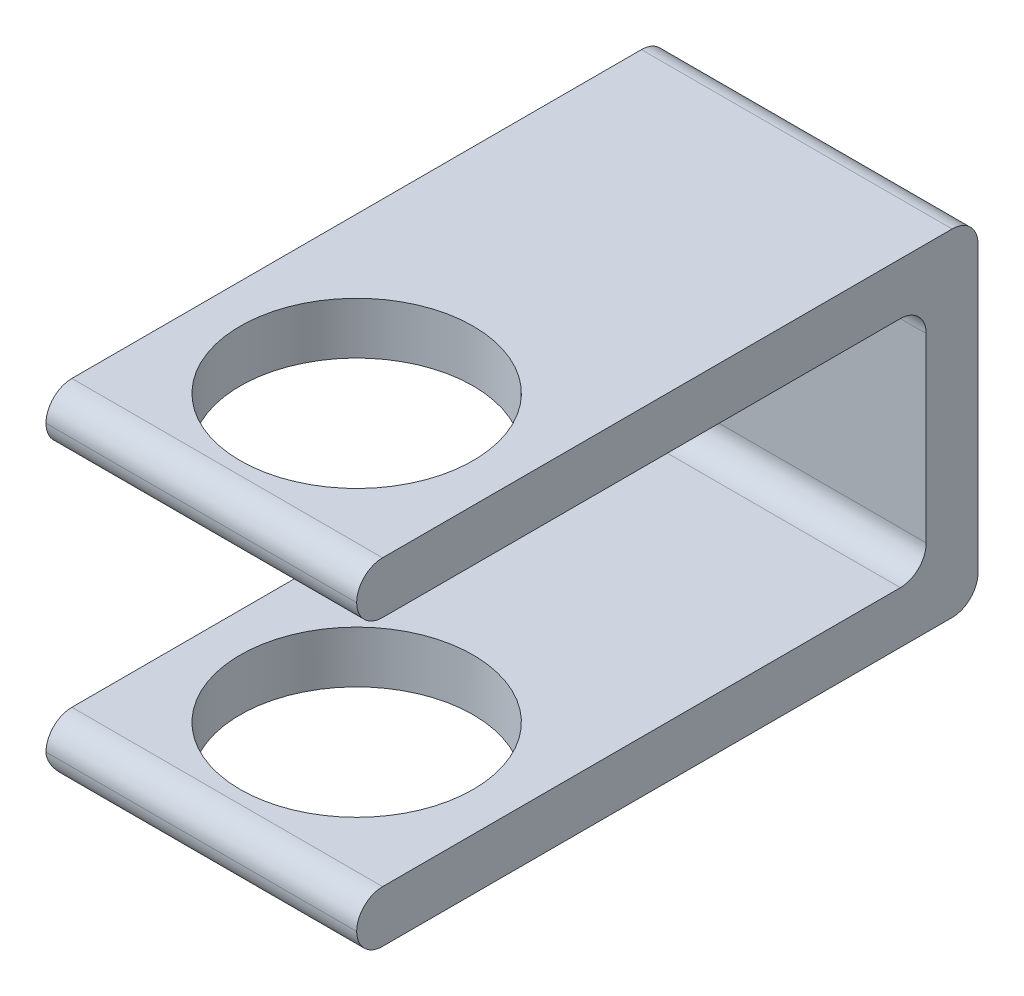
SolidWorks part; units mm, degrees
ref_plane "Front Plane" through (0, 0, 0) normal (0, 0, 1) x (1, 0, 0)
ref_plane "Top Plane" through (0, 0, 0) normal (0, 1, 0) x (1, 0, 0)
ref_plane "Right Plane" through (0, 0, 0) normal (1, 0, 0) x (0, 0, -1)
sketch "Sketch1" plane through (0, 0, 0) normal (0, 1, 0) x (1, 0, 0)
  line L1 (-19.05, -38.1) -> (19.05, -38.1)
  line L2 (-19.05, -38.1) -> (-19.05, 38.1)
  line L3 (-19.05, 38.1) -> (19.05, 38.1)
  line L4 (19.05, -38.1) -> (19.05, 38.1)
  line L5 (-19.05, -38.1) -> (19.05, 38.1) construction
  line L6 (-19.05, 38.1) -> (19.05, -38.1) construction
  point P0 (0, 0)
  dimension "D1" = 38.1
  dimension "D2" = 76.2
extrude "Boss-Extrude1" add sketch "Sketch1" along normal blind 41.275
sketch "Sketch2" plane through (0, 0, 38.1) normal (0, 0, 1) x (1, 0, 0)
  line L0 (-19.05, 41.275) -> (-19.05, 0) construction
  line L1 (-19.05, 34.925) -> (19.05, 34.925)
  line L2 (-19.05, 34.925) -> (-19.05, 6.35)
  line L3 (-19.05, 6.35) -> (19.05, 6.35)
  line L4 (19.05, 34.925) -> (19.05, 6.35)
  line L5 (19.05, 41.275) -> (19.05, 0) construction
  line L6 (-19.05, 41.275) -> (19.05, 41.275) construction
  line L7 (-19.05, 0) -> (19.05, 0) construction
  dimension "D1" = 6.35
  dimension "D2" = 6.35
extrude "Cut-Extrude1" cut sketch "Sketch2" against normal offset from surface (69.85 mm away) 6.35 up to face at (0, 20.6375, -38.1)
sketch "Sketch3" plane through (0, 41.275, 0) normal (0, 1, 0) x (1, 0, 0)
  line L1 (19.05, 38.1) -> (-19.05, 38.1) construction
  line L3 (3.6662, -12.7) -> (-3.6662, -12.7)
  line L4 (-3.6662, -12.7) -> (-7.3323, -19.05)
  line L5 (-7.3323, -19.05) -> (-3.6662, -25.4)
  line L6 (-3.6662, -25.4) -> (3.6662, -25.4)
  line L7 (3.6662, -25.4) -> (7.3323, -19.05)
  line L8 (7.3323, -19.05) -> (3.6662, -12.7)
  circle A0 centre (0, -19.05) radius 50.8
  circle A1 centre (0, -19.05) radius 6.35 construction
  circle A2 centre (0, -19.05) radius 14.2875
  dimension "D1" = 101.6
  dimension "D2" = 6.35
  dimension "D3" = 12.7
  dimension "D4" = 28.575
extrude "Cut-Extrude2" cut sketch "Sketch3" against normal through all contours L7 L8 L3 L4 L5 L6 | A2 L8 L7 L6 L5 L4 L3 region at (0, 41.275, 19.05) region at (-13.8834, 41.275, 19.05)
fillet "Fillet1" radius 3.175 9 edges at (0, 41.275, 38.1) (0, 0, -38.1) (0, 0, 38.1) (0, 6.35, 38.1) (0, 6.35, -31.75) (0, 34.925, -31.75) (0, 34.925, 38.1) (0, 41.275, -38.1) (-19.05, 0, 0)
